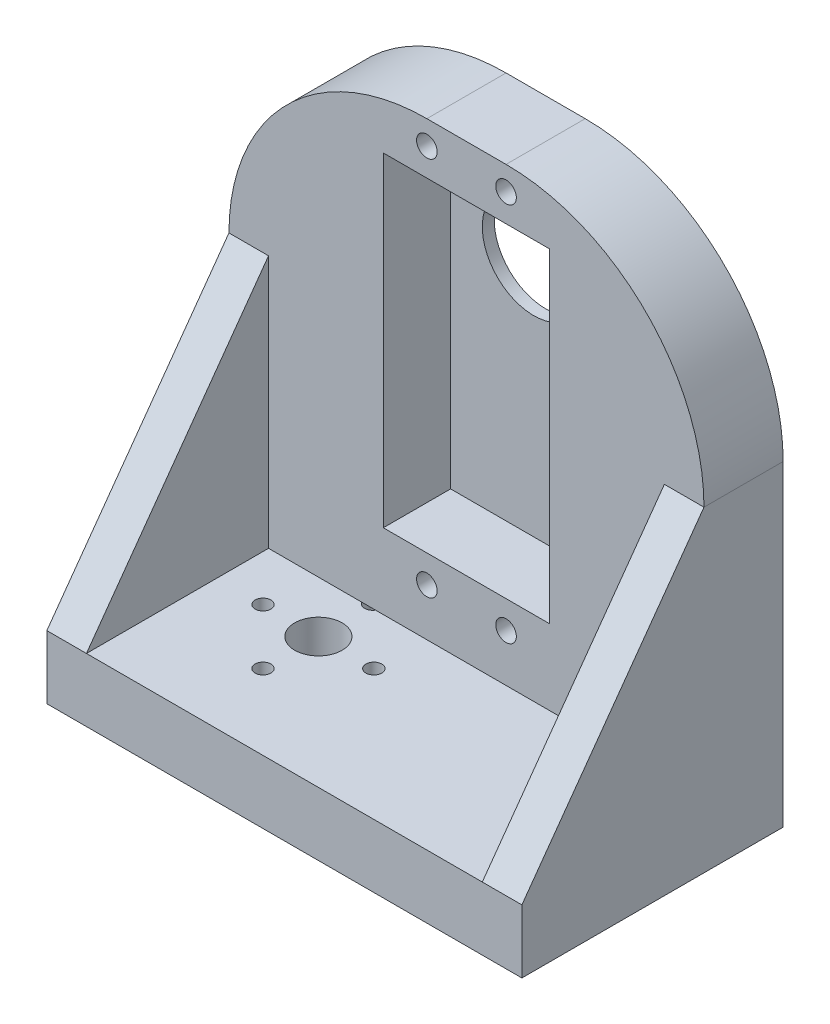
SolidWorks part; units mm, degrees
ref_plane "Front Plane" through (0, 0, 0) normal (0, 0, 1) x (1, 0, 0)
ref_plane "Top Plane" through (0, 0, 0) normal (0, 1, 0) x (1, 0, 0)
ref_plane "Right Plane" through (0, 0, 0) normal (1, 0, 0) x (0, 0, -1)
sketch "Sketch2" plane through (0, 0, 0) normal (0, 1, 0) x (1, 0, 0)
  line L1 (-30, -16.5) -> (30, -16.5)
  line L2 (-30, -16.5) -> (-30, 16.5)
  line L3 (-30, 16.5) -> (30, 16.5)
  line L4 (30, -16.5) -> (30, 16.5)
  line L5 (-30, -16.5) -> (30, 16.5) construction
  line L6 (-30, 16.5) -> (30, -16.5) construction
  point P0 (0, 0)
  dimension "D1" = 60
  dimension "D2" = 33
extrude "Boss-Extrude1" add sketch "Sketch2" along normal blind 65
sketch "Sketch3" plane through (-30, 0, 0) normal (-1, 0, 0) x (0, 0, 1)
  line L0 (-16.5, 65) -> (16.5, 65) construction
  line L1 (-6.5, 65) -> (16.5, 65)
  line L2 (-6.5, 65) -> (-6.5, 8)
  line L3 (-6.5, 8) -> (16.5, 8)
  line L4 (16.5, 65) -> (16.5, 8)
  line L5 (16.5, 65) -> (16.5, 0) construction
  line L6 (-16.5, 65) -> (-16.5, 0) construction
  line L7 (-16.5, 0) -> (16.5, 0) construction
  dimension "D1" = 10
  dimension "D2" = 8
extrude "Cut-Extrude1" cut sketch "Sketch3" against normal blind 60
sketch "Sketch4" plane through (0, 0, -6.5) normal (0, 0, 1) x (1, 0, 0)
  line L0 (0, 62.0464) -> (0, -3.8896) construction
  line L1 (-30, 38) -> (30.8316, 38) construction
  line L2 (-30, 65) -> (-30, 8) construction
  line L3 (30, 65) -> (-30, 65) construction
  line L5 (-10.5, 17.5) -> (10.5, 17.5)
  line L6 (-10.5, 17.5) -> (-10.5, 58.5)
  line L7 (-10.5, 58.5) -> (10.5, 58.5)
  line L8 (10.5, 17.5) -> (10.5, 58.5)
  line L9 (-10.5, 17.5) -> (10.5, 58.5) construction
  line L10 (-10.5, 58.5) -> (10.5, 17.5) construction
  circle A0 centre (-5, 62) radius 1.3
  circle A1 centre (5, 62) radius 1.3
  circle A2 centre (5, 14) radius 1.3
  circle A3 centre (-5, 14) radius 1.3
  point P9 (0, 38)
  dimension "D4" = 2.6
  dimension "D1" = 27
  dimension "D2" = 21
  dimension "D3" = 41
  dimension "D5" = 3.5
  dimension "D6" = 10
extrude "Cut-Extrude2" cut sketch "Sketch4" against normal blind 8.5 contours L5 L8 L7 L6 region at (0, 38, -6.5)
extrude "Cut-Extrude3" cut sketch "Sketch4<3>" against normal through all contours A2 | A0 | A1 | A3 region at (5, 14, -6.5)
sketch "Sketch4<3>" plane through (0, 0, -6.5) normal (0, 0, 1) x (1, 0, 0) same geometry as "Sketch4"
sketch "Sketch6" plane through (0, 0, 0) normal (0, -1, 0) x (1, 0, 0)
  line L0 (-30, -16.5) -> (-30, 16.5) construction
  circle A0 centre (-12.2, 0) radius 3
  circle A1 centre (-5.2, 0) radius 1
  circle A2 centre (-19.2, 0) radius 1
  circle A3 centre (-12.2, 7) radius 1
  circle A4 centre (-12.2, -7) radius 1
  dimension "D1" = 6
  dimension "D2" = 2
  dimension "D3" = 2
  dimension "D9" = 2
  dimension "D10" = 2
  dimension "D4" = 14
  dimension "D5" = 7
  dimension "D6" = 17.8
  dimension "D7" = 7
  dimension "D8" = 7
extrude "Cut-Extrude4" cut sketch "Sketch6" against normal through all contours A0 | A2 | A1 | A3 region at (-12.2, 0, 0) region at (-19.2, 0, 0)
fillet "Fillet2" radius 25 1 edges at (-30, 65, -11.5) type face fillet first side face at (-30, 24.3333, -2.1667) second side face at (0, 65, -11.5)
fillet "Fillet4" radius 25 1 edges at (30, 65, -11.5) type face fillet first side face at (30, 24.3333, -2.1667) second side face at (12.5, 65, -11.5)
sketch "Sketch8" plane through (-30, 0, 0) normal (-1, 0, 0) x (0, 0, 1)
  line L0 (-6.5, 40) -> (16.5, 8)
  line L1 (16.5, 8) -> (-6.5, 8)
  line L2 (-6.5, 8) -> (-6.5, 40)
extrude "Boss-Extrude2" add sketch "Sketch8" against normal blind 5
mirror "Mirror1" about plane through (0, 0, 0) normal (1, 0, 0) of "Boss-Extrude2"
sketch "Sketch9" plane through (0, 0, -15) normal (0, 0, 1) x (1, 0, 0)
  line L0 (-10.5, 58.5) -> (10.5, 58.5) construction
  circle A0 centre (0, 48.2) radius 6.5
  dimension "D1" = 13
  dimension "D2" = 10.3
extrude "Cut-Extrude5" cut sketch "Sketch9" against normal through all
sketch "Sketch10" plane through (0, 0, 0) normal (0, -1, 0) x (1, 0, 0)
  line L0 (-12.2, 9.6381) -> (-12.2, -9.6612) construction
  line L1 (-26.2629, 0) -> (3.8865, 0) construction
  circle A0 centre (-12.2, 0) radius 10.5
  dimension "D1" = 21
extrude "Cut-Extrude6" cut sketch "Sketch10" against normal blind 2.3
sketch "Sketch12" plane through (0, 2.3, 0) normal (0, -1, 0) x (1, 0, 0)
  circle A0 centre (-12.3509, -7) radius 1
  dimension "D2" = 2
  dimension "D1" = 7
extrude "Cut-Extrude7" cut sketch "Sketch12" against normal up to vertex (5.7 mm away) up to point (-25, 8, -6.5)
